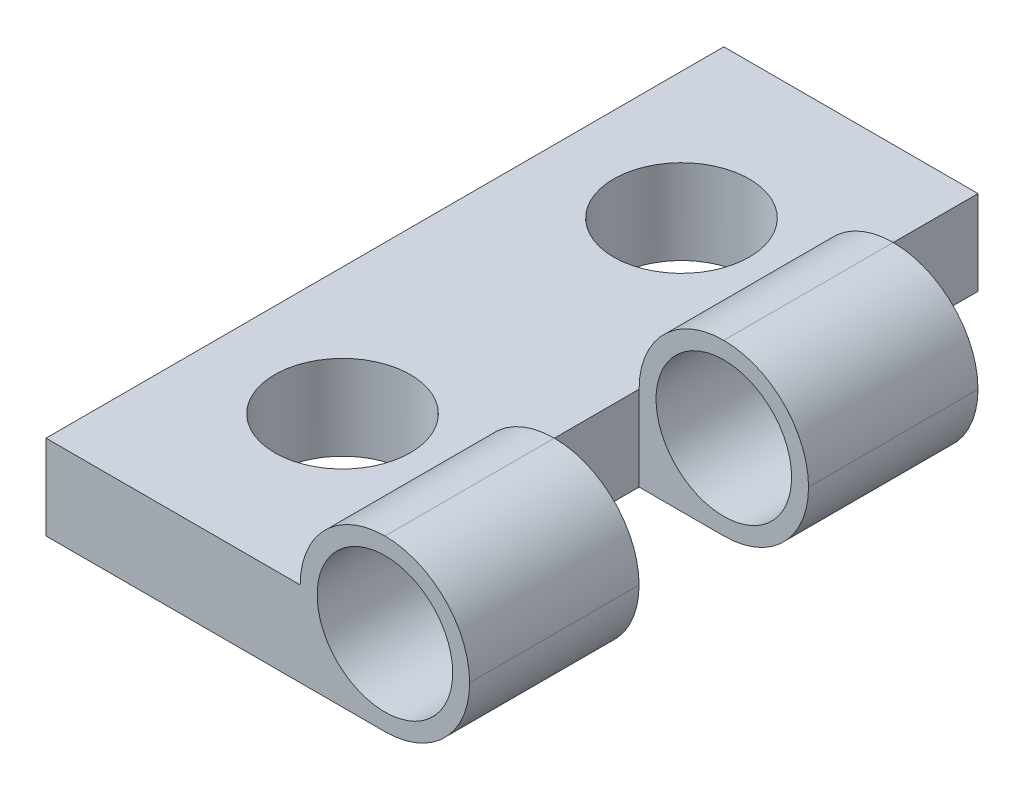
SolidWorks part; units mm, degrees
material "1.4000 (X6Cr13)"
ref_plane "Płaszczyzna przednia" through (0, 0, 0) normal (0, 0, 1) x (1, 0, 0)
ref_plane "Płaszczyzna górna" through (0, 0, 0) normal (0, 1, 0) x (1, 0, 0)
ref_plane "Płaszczyzna prawa" through (0, 0, 0) normal (1, 0, 0) x (0, 0, -1)
sketch "Szkic1" plane through (0, 0, 0) normal (0, 1, 0) x (1, 0, 0)
  line L1 (-7.5, -20) -> (7.5, -20)
  line L2 (-7.5, -20) -> (-7.5, 20)
  line L3 (-7.5, 20) -> (7.5, 20)
  line L4 (7.5, -20) -> (7.5, 20)
  line L5 (-7.5, -20) -> (7.5, 20) construction
  line L6 (-7.5, 20) -> (7.5, -20) construction
  point P0 (0, 0)
  dimension "D1" = 15
  dimension "D2" = 40
extrude "Dodanie-wyciągnięcie1" add sketch "Szkic1" along normal blind 5
sketch "Szkic2" plane through (7.5, 0, 0) normal (1, 0, 0) x (0, 0, -1)
  line L0 (-20, 0) -> (20, 0) construction
  line L1 (-20, 0) -> (-10, 0)
  line L2 (-20, 0) -> (-20, 10)
  line L3 (-20, 10) -> (-10, 10)
  line L4 (-10, 0) -> (-10, 10)
  line L5 (0, 0) -> (10, 0)
  line L6 (0, 0) -> (0, 10)
  line L7 (0, 10) -> (10, 10)
  line L8 (10, 0) -> (10, 10)
  dimension "D1" = 10
  dimension "D2" = 10
  dimension "D3" = 10
  dimension "D4" = 10
extrude "Dodanie-wyciągnięcie2" add sketch "Szkic2" along normal blind 10
sketch "Szkic3" plane through (0, 0, 20) normal (0, 0, 1) x (1, 0, 0)
  line L0 (7.5, 10) -> (17.5, 0) construction
  circle A0 centre (12.5, 5) radius 4
extrude "Wytnij-wyciągnięcie1" cut sketch "Szkic3" against normal blind 30
fillet "Zaokrąglenie1" radius 5 6 edges at (7.5, 10, 15) (7.5, 10, -5) (17.5, 0, 15) (17.5, 0, -5) (17.5, 10, -5) (17.5, 10, 15)
sketch "Szkic4" plane through (0, 5, 0) normal (0, 1, 0) x (1, 0, 0)
  line L0 (7.5, 10) -> (-7.5, 10) construction
  line L1 (-7.5, 20) -> (-7.5, -20) construction
  line L2 (7.5, -10) -> (-7.5, -10) construction
  circle A0 centre (0, 10) radius 4
  circle A1 centre (0, -10) radius 4
extrude "Wytnij-wyciągnięcie2" cut sketch "Szkic4" against normal blind 30
